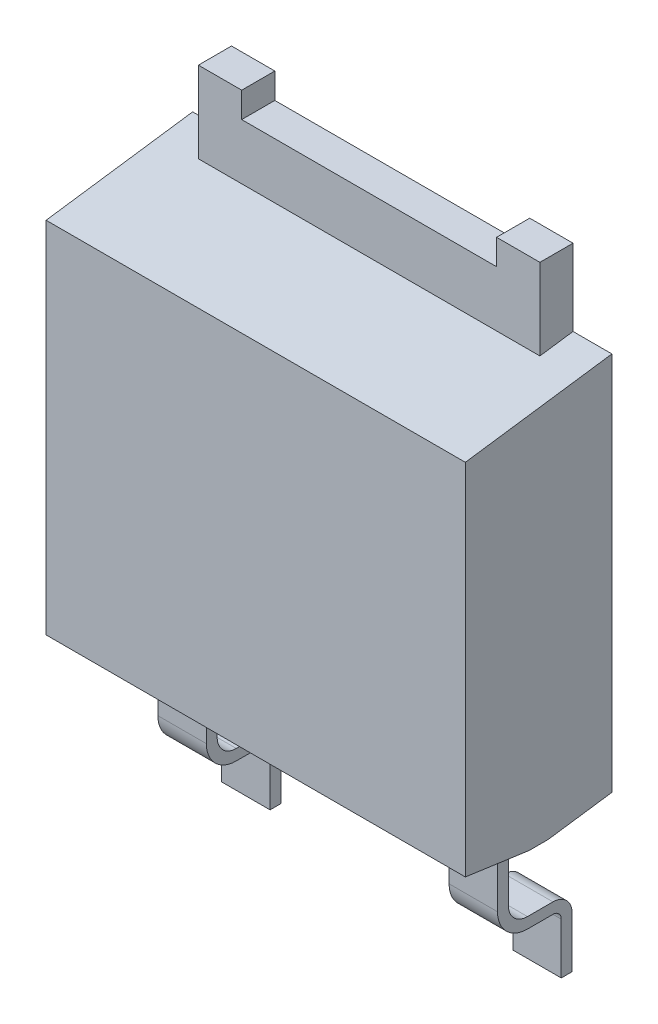
SolidWorks part; units mm, degrees
ref_plane "Front Plane" through (0, 0, 0) normal (0, 0, 1) x (1, 0, 0)
ref_plane "Top Plane" through (0, 0, 0) normal (0, 1, 0) x (1, 0, 0)
ref_plane "Right Plane" through (0, 0, 0) normal (1, 0, 0) x (0, 0, -1)
sketch "Sketch1" plane through (0, 0, 0) normal (0, 0, 1) x (1, 0, 0)
  line L1 (0, 0) -> (6.58, 0)
  line L2 (0, 0) -> (0, 6.1)
  line L3 (0, 6.1) -> (6.58, 6.1)
  line L4 (6.58, 0) -> (6.58, 6.1)
  dimension "D1" = 6.1
  dimension "D2" = 6.58
extrude "Boss-Extrude1" add sketch "Sketch1" along normal blind 2.3
draft "Draft1" type of draft neutral plane draft angle 8 faces to draft 1 face at (3.29, 6.1, 1.15) neutral plane through (0, 0, 0) neutral plane normal (0, 0, -1) reverse direction yes parameters "D1"=8
ref_plane "Plane1" through (0, 0, 1.01) normal (0, 0, 1) x (1, 0, 0)
ref_plane "Plane2" through (0, 0, 1.18) normal (0, 0, 1) x (1, 0, 0)
ref_axis "Axis1" through (6.58, 0, 1.18) along (-1, 0, 0)
chamfer "Chamfer1" distance 1 angle 8 2 edges at (3.29, 0, 0) (3.29, 0, 2.3) first distance on face at (3.29, 0, 1.15)
sketch "Sketch2" plane through (0, 0, 0) normal (0, 0, 1) x (1, 0, 0)
  line L0 (6.58, 6.1) -> (0, 6.1) construction
  line L1 (0.61, 5.7768) -> (5.97, 5.7768)
  line L2 (0.61, 6.1) -> (0.61, 7.3)
  line L3 (0.61, 7.3) -> (1.29, 7.3)
  line L4 (5.97, 6.1) -> (5.97, 7.3)
  line L5 (3.29, 0.1405) -> (3.29, 7.3) construction
  line L6 (0, 0.1405) -> (6.58, 0.1405) construction
  line L7 (5.29, 7.3) -> (5.97, 7.3)
  line L8 (6.58, 5.7768) -> (0, 5.7768) construction
  line L9 (1.29, 7.3) -> (1.29, 6.9)
  line L10 (1.29, 6.9) -> (5.29, 6.9)
  line L11 (5.29, 7.3) -> (5.29, 6.9)
  line L12 (5.97, 5.7768) -> (5.97, 6.1)
  line L13 (0.61, 6.1) -> (0.61, 5.7768)
  point P15 (3.29, 6.9)
  dimension "D1" = 5.36
  dimension "D3" = 0.4
  dimension "D4" = 4
extrude "Boss-Extrude2" add sketch "Sketch2" along normal blind 0.52
ref_plane "Plane3" through (3.29, 0, 0) normal (1, 0, 0) x (0, 0, -1)
ref_plane "Plane4" through (5.575, 0, 0) normal (1, 0, 0) x (0, 0, -1)
sketch "Sketch3" plane through (5.575, 0, 0) normal (1, 0, 0) x (0, 0, -1)
  line L0 (-1, 0) -> (-1, -1.21)
  line L1 (-0.7, -1.51) -> (-0.3, -1.51)
  line L2 (0, -1.81) -> (0, -2.61)
  line L3 (-0.52, 7.3) -> (0, 7.3) construction
  arc A0 (-0.7, -1.51) -> (-1, -1.21) centre (-0.7, -1.21) cw
  arc A1 (0, -1.81) -> (-0.3, -1.51) centre (-0.3, -1.81) ccw
  dimension "D3" = 0.3
  dimension "D1" = 1.1
  dimension "D2" = 9.91
extrude "Extrude-Thin1" add sketch "Sketch3" along normal mid plane 0.76 thin thin type one direction wall 0.17
mirror "Mirror1" about plane through (3.29, 0, 0) normal (1, 0, 0) of "Extrude-Thin1"
sketch "Sketch4" plane through (3.29, 0, 0) normal (1, 0, 0) x (0, 0, -1)
  line L0 (-1, 0) -> (-1, -0.83)
  line L1 (-1, 0) -> (-1, -1.21) construction
  dimension "D1" = 0.83
extrude "Extrude-Thin2" add sketch "Sketch4" along normal mid plane 0.76 thin thin type one direction wall 0.17
